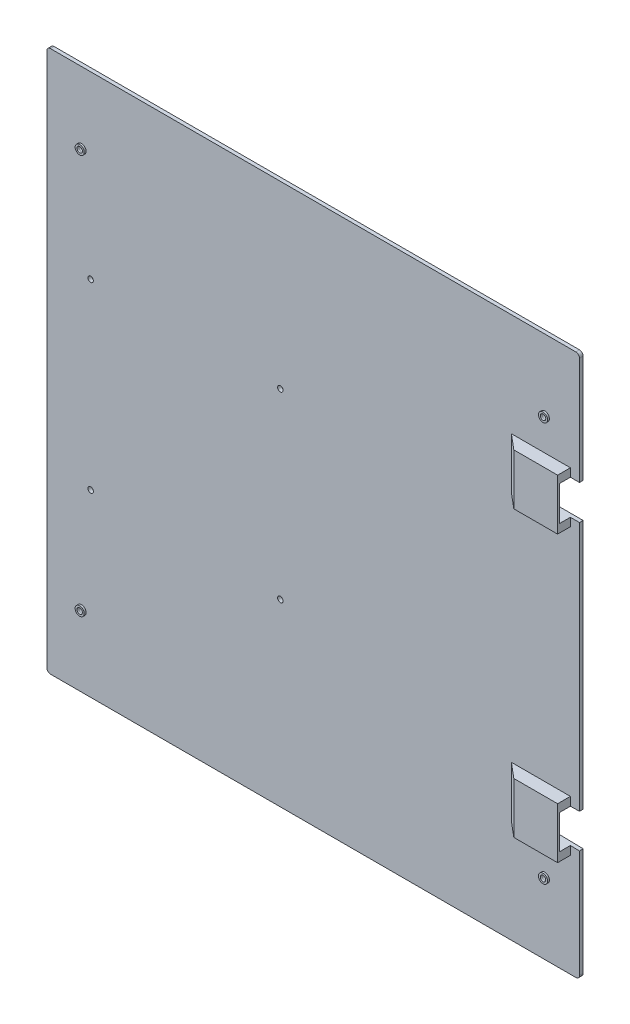
SolidWorks part; units mm, degrees
ref_plane "Front Plane" through (0, 0, 0) normal (0, 0, 1) x (1, 0, 0)
ref_plane "Top Plane" through (0, 0, 0) normal (0, 1, 0) x (1, 0, 0)
ref_plane "Right Plane" through (0, 0, 0) normal (1, 0, 0) x (0, 0, -1)
sketch "Sketch1" plane through (0, 0, 0) normal (0, 0, 1) x (1, 0, 0)
  line L0 (0, 2) -> (288, 2)
  line L1 (-2, 0) -> (-2, -293)
  line L2 (0, -295) -> (288, -295)
  line L3 (290, 0) -> (290, -293)
  arc A0 (288, 2) -> (290, 0) centre (288, 0) cw
  arc A1 (288, -295) -> (290, -293) centre (288, -293) ccw
  arc A2 (-2, -293) -> (0, -295) centre (0, -293) ccw
  arc A3 (0, 2) -> (-2, 0) centre (0, 0) ccw
  dimension "D3" = 2
  dimension "D1" = 297
  dimension "D2" = 292
extrude "Boss-Extrude1" add sketch "Sketch1" along normal blind 2
sketch "Sketch4" plane through (0, 0, 0) normal (0, 0, -1) x (-1, 0, 0)
  line L0 (-144, 2) -> (-144, -295) construction
  line L1 (-288, 2) -> (0, 2) construction
  line L2 (0, -295) -> (-288, -295) construction
  line L3 (-290, -146.5) -> (2, -146.5) construction
  line L4 (-290, -293) -> (-290, 0) construction
  line L5 (2, 0) -> (2, -293) construction
  line L6 (-290, -293) -> (-290, 0) construction
  line L7 (0, -295) -> (-288, -295) construction
  circle A7 centre (-271, -256) radius 1.6
  circle A8 centre (-271, -37) radius 1.6
  circle A9 centre (-17, -256) radius 1.6
  circle A10 centre (-17, -37) radius 1.6
  dimension "D1" = 19
  dimension "D2" = 39
  dimension "D3" = 3.2
extrude "Cut-Extrude4" cut sketch "Sketch4" against normal through all
sketch "Sketch3" plane through (0, 0, 2) normal (0, 0, -1) x (-1, 0, 0)
  line L1 (-290, -293) -> (-290, 0) construction
  line L2 (-144, 2) -> (-144, -295) construction
  line L3 (-288, 2) -> (0, 2) construction
  line L4 (0, -295) -> (-288, -295) construction
  line L5 (-290, -146.5) -> (2, -146.5) construction
  line L6 (2, 0) -> (2, -293) construction
  circle A0 centre (-271, -37) radius 1.5
  circle A1 centre (-271, -37) radius 2.5
  circle A2 centre (-17, -37) radius 2.5
  circle A3 centre (-17, -37) radius 1.5
  circle A4 centre (-17, -256) radius 1.5
  circle A5 centre (-17, -256) radius 2.5
  circle A6 centre (-271, -256) radius 2.5
  circle A7 centre (-271, -256) radius 1.5
  dimension "D1" = 3
  dimension "D2" = 5
extrude "Boss-Extrude3" add sketch "Sketch3" against normal blind 1
ref_plane "Plane2" through (19.4263, 0, -72.5) normal (0.2588, 0, -0.9659) x (0, 1, 0)
sketch "Sketch5" plane through (0, 0, 2) normal (0, 0, 1) x (1, 0, 0)
  line L7 (-2, 0) -> (-2, -293) construction
  line L13 (261, -54.5) -> (285, -54.5)
  line L14 (261, -54.5) -> (261, -82.5)
  line L15 (261, -82.5) -> (285, -82.5)
  line L16 (285, -54.5) -> (285, -82.5)
  line L17 (288, 2) -> (0, 2) construction
  line L18 (-2, -146.5) -> (290, -146.5) construction
  line L19 (290, -293) -> (290, 0) construction
  line L20 (285, -238.5) -> (285, -210.5)
  line L21 (261, -210.5) -> (285, -210.5)
  line L22 (261, -238.5) -> (261, -210.5)
  line L23 (261, -238.5) -> (285, -238.5)
  dimension "D1" = 28
  dimension "D2" = 24
  dimension "D3" = 56.5
  dimension "D4" = 5
extrude "Boss-Extrude2" add sketch "Sketch5" along normal blind 7
sketch "Sketch2" plane through (19.3605, 0, -72.5176) normal (-0.2588, 0, 0.9659) x (0, -1, 0)
  line L0 (-2, 278.7724) -> (-2, 0.5858) construction
  line L1 (234, 285.7043) -> (215, 285.7043)
  line L2 (234, 285.7043) -> (234, 261.1866) construction
  line L3 (234, 261.1866) -> (215, 261.1866) construction
  line L4 (215, 285.7043) -> (215, 261.1866) construction
  line L5 (146.5, 307.7502) -> (146.5, -283.1376) construction
  line L6 (215.5, 261.1866) -> (233.5, 261.1866)
  line L7 (224.5, 285.7043) -> (224.5, 288.2326) construction
  line L8 (293, 280.1866) -> (0, 280.1866) construction
  line L9 (293, 280.7043) -> (0, 280.7043) construction
  line L10 (234, 285.7043) -> (234, 261.1866) construction
  line L11 (215, 285.7043) -> (215, 261.1866) construction
  line L12 (65, 287.2326) -> (65, 312.7502) construction
  line L13 (78, 285.7043) -> (78, 261.1866)
  line L14 (59, 285.7043) -> (59, 261.1866)
  line L15 (78, 285.7043) -> (78, 261.1866)
  line L16 (59, 261.1866) -> (78, 261.1866)
  line L17 (59, 285.7043) -> (59, 261.1866)
  line L18 (59, 285.7043) -> (78, 285.7043)
  line L19 (295, 0.5858) -> (295, 278.7724) construction
  line L21 (238.5, 254.5042) -> (238.5, 277.6864) construction
  line L23 (215, 285.7043) -> (215.5, 261.1866)
  line L24 (234, 285.7043) -> (233.5, 261.1866)
  line L25 (210.5, 275.8746) -> (210.5, 252.6924) construction
  dimension "D1" = 19
  dimension "D2" = 5
  dimension "D4" = 19
  dimension "D5" = 0.5
  dimension "D6" = 0.5
extrude "Cut-Extrude5" cut sketch "Sketch2" along normal blind 9 contours L4 L1 L2 L3 | L14 L18 L13 L16
ref_plane "Plane3" through (103.4073, 0, -123.236) normal (-0.6428, 0, 0.766) x (0, -1, 0)
sketch "Sketch8" plane through (103.4073, 0, -123.236) normal (-0.6428, 0, 0.766) x (0, -1, 0)
  line L0 (146.5, 368.5012) -> (146.5, -706.828) construction
  line L1 (82.5, 205.7227) -> (54.5, 205.7227)
  line L2 (82.5, 205.7227) -> (82.5, 181.7227)
  line L3 (82.5, 181.7227) -> (54.5, 181.7227)
  line L4 (54.5, 205.7227) -> (54.5, 181.7227)
  line L12 (-2, 221.9064) -> (-2, 1.2856) construction
  line L13 (295, 1.2856) -> (295, 221.9064) construction
  line L14 (238.5, 205.7227) -> (238.5, 181.7227)
  line L15 (210.5, 181.7227) -> (238.5, 181.7227)
  line L16 (210.5, 205.7227) -> (210.5, 181.7227)
  line L17 (210.5, 205.7227) -> (238.5, 205.7227)
  dimension "D1" = 24
extrude "Boss-Extrude4" add sketch "Sketch8" along normal up to surface (9.1379 mm away)
sketch "Sketch9" plane through (0, 0, 0) normal (0, 0, -1) x (-1, 0, 0)
  circle A0 centre (-126, -196.5) radius 1.5
  circle A1 centre (-126, -96.5) radius 1.5
  circle A2 centre (-22, -96.5) radius 1.5
  circle A3 centre (-22, -196.5) radius 1.5
  dimension "D1" = 3
extrude "Cut-Extrude7" cut sketch "Sketch9" against normal through all
